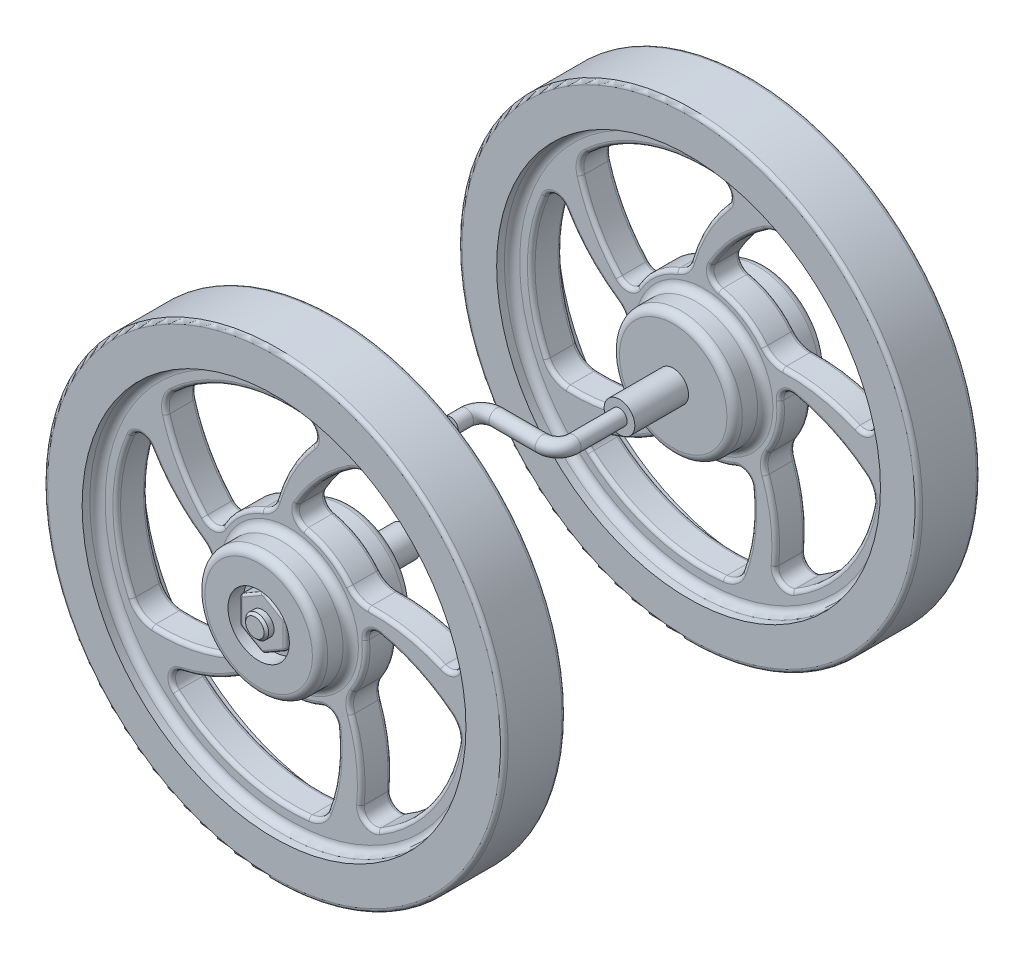
SolidWorks part; units mm, degrees
material "AISI 1020"
ref_plane "Спереди" through (0, 0, 0) normal (0, 0, 1) x (1, 0, 0)
ref_plane "Сверху" through (0, 0, 0) normal (0, 1, 0) x (1, 0, 0)
ref_plane "Справа" through (0, 0, 0) normal (1, 0, 0) x (0, 0, -1)
sketch "Эскиз1" plane through (0, 0, 0) normal (0, 1, 0) x (1, 0, 0)
  line L0 (-352.3825, 0) -> (377.342, 0) construction
  line L1 (0, 174.0357) -> (0, -175.3971) construction
  line L2 (0, -140) -> (0, -80)
  line L3 (-20, -60) -> (-80, -60)
  line L4 (-100, -40) -> (-100, 40)
  line L5 (0, 140) -> (0, 80)
  line L6 (-20, 60) -> (-80, 60)
  arc A0 (-100, -40) -> (-80, -60) centre (-80, -40) ccw
  arc A1 (-20, -60) -> (0, -80) centre (-20, -80) cw
  arc A2 (-20, 60) -> (0, 80) centre (-20, 80) ccw
  arc A3 (-100, 40) -> (-80, 60) centre (-80, 40) cw
  point P13 (0, -60)
  point P21 (-100, 0)
  dimension "D4" = 20
  dimension "D1" = 140
  dimension "D2" = 80
  dimension "D3" = 100
ref_plane "Плоскость1" through (0, 0, 140) normal (0, 0, -1) x (-1, 0, 0)
sketch "Эскиз2" plane through (0, 0, 140) normal (0, 0, -1) x (-1, 0, 0)
  circle A0 centre (0, 0) radius 10
  dimension "D1" = 20
sweep "По траектории1" add profiles "Эскиз2" path "Эскиз1"
sketch "Эскиз3" plane through (0, 0, 0) normal (0, 1, 0) x (1, 0, 0)
  line L0 (0, 150.9872) -> (0, -160.0129) construction
  line L1 (-100, 40) -> (-100, -40) construction
  line L2 (-110, 40) -> (-90, 40) construction
  line L3 (-110, -40) -> (-90, -40) construction
  line L4 (-166.6895, 0) -> (41.4175, 0) construction
  line L5 (-90, -40) -> (-90, 40) construction
  line L6 (-90, 20) -> (-95, 20)
  line L7 (-90, 20) -> (-90, -20)
  line L9 (-95, 20) -> (-95, -20)
  line L10 (-90, -20) -> (-95, -20)
  point P18 (-90, 0)
  point P19 (-95, 0)
  dimension "D1" = 20
  dimension "D2" = 5
revolve "Вырез-Повернуть1" cut sketch "Эскиз3" angle 360 about L1
sketch "Эскиз4" plane through (0, 0, 0) normal (1, 0, 0) x (0, 0, -1)
  line L0 (0, 86.383) -> (0, -119.6609) construction
  line L1 (-305.5987, 0) -> (289.4148, 0) construction
  line L2 (140, 0) -> (140, 20)
  line L3 (-140, 0) -> (-210, 0)
  line L4 (-140, 0) -> (-140, 20)
  line L5 (-140, 20) -> (-210, 20)
  line L6 (-210, 0) -> (-210, 20)
  line L7 (140, 0) -> (210, 0)
  line L8 (140, 20) -> (210, 20)
  line L9 (210, 0) -> (210, 20)
  dimension "D1" = 20
  dimension "D2" = 210
revolve "Повернуть1" add sketch "Эскиз4" angle 360 about L1
sketch "Эскиз5" plane through (0, 0, 0) normal (1, 0, 0) x (0, 0, -1)
  line L0 (-556.9383, 0) -> (336.2092, 0) construction
  line L1 (0, 98.9939) -> (0, -140.8119) construction
  line L2 (-270, 411.7302) -> (-270, -180.2981) construction
  line L3 (-210, 20) -> (-210, -20) construction
  line L4 (-210, 0) -> (-210, 70)
  line L5 (-220, 80) -> (-240, 80)
  line L6 (-250, 90) -> (-250, 240)
  line L7 (-240, 250) -> (-230, 250)
  line L8 (-230, 250) -> (-230, 300)
  line L9 (-230, 300) -> (-310, 300)
  line L10 (-320, 80) -> (-300, 80)
  line L11 (-290, 90) -> (-290, 240)
  line L12 (-300, 250) -> (-310, 250)
  line L13 (-310, 250) -> (-310, 300)
  line L14 (-330, 70) -> (-330, 40)
  line L15 (-330, 40) -> (-310, 40)
  line L16 (-310, 40) -> (-310, 0)
  line L17 (-310, 0) -> (-210, 0)
  line L18 (230, 250) -> (230, 300)
  line L19 (240, 250) -> (230, 250)
  line L20 (250, 90) -> (250, 240)
  line L21 (220, 80) -> (240, 80)
  line L22 (210, 0) -> (210, 70)
  line L23 (310, 0) -> (210, 0)
  line L24 (310, 40) -> (310, 0)
  line L25 (330, 40) -> (310, 40)
  line L26 (330, 70) -> (330, 40)
  line L27 (320, 80) -> (300, 80)
  line L28 (290, 90) -> (290, 240)
  line L29 (300, 250) -> (310, 250)
  line L30 (310, 250) -> (310, 300)
  line L31 (230, 300) -> (310, 300)
  arc A0 (-250, 240) -> (-240, 250) centre (-240, 240) cw
  arc A1 (-250, 90) -> (-240, 80) centre (-240, 90) ccw
  arc A2 (-210, 70) -> (-220, 80) centre (-220, 70) ccw
  arc A3 (-330, 70) -> (-320, 80) centre (-320, 70) cw
  arc A4 (-290, 90) -> (-300, 80) centre (-300, 90) cw
  arc A5 (-290, 240) -> (-300, 250) centre (-300, 240) ccw
  arc A6 (250, 240) -> (240, 250) centre (240, 240) ccw
  arc A7 (250, 90) -> (240, 80) centre (240, 90) cw
  arc A8 (210, 70) -> (220, 80) centre (220, 70) cw
  arc A9 (330, 70) -> (320, 80) centre (320, 70) ccw
  arc A10 (290, 90) -> (300, 80) centre (300, 90) ccw
  arc A11 (290, 240) -> (300, 250) centre (300, 240) cw
  point P35 (-270, 300)
  dimension "D7" = 10
  dimension "D1" = 60
  dimension "D2" = 300
  dimension "D3" = 80
  dimension "D4" = 20
  dimension "D5" = 40
  dimension "D6" = 50
  dimension "D8" = 40
  dimension "D9" = 20
revolve "Повернуть2" add sketch "Эскиз5" angle 360 about L0
fillet "Скругление1" radius 5 4 edges at (300, 0, -230) (300, 0, -310) (300, 0, 230) (300, 0, 310)
sketch "Эскиз6" plane through (0, 0, 310) normal (0, 0, 1) x (1, 0, 0)
  line L0 (0, 322.762) -> (0, -326.0866) construction
  line L2 (-2.5, 33.1976) -> (-27.5, 18.7639)
  line L3 (-30, 14.4338) -> (-30, -14.4338)
  line L4 (-27.5, -18.7639) -> (-2.5, -33.1976)
  line L5 (2.5, -33.1976) -> (27.5, -18.7639)
  line L6 (30, -14.4338) -> (30, 14.4338)
  line L7 (27.5, 18.7639) -> (2.5, 33.1976)
  circle A0 centre (0, 0) radius 30 construction
  arc A1 (27.5, 18.7639) -> (30, 14.4338) centre (25, 14.4338) cw
  arc A2 (30, -14.4338) -> (27.5, -18.7639) centre (25, -14.4338) cw
  arc A3 (2.5, -33.1976) -> (-2.5, -33.1976) centre (0, -28.8675) cw
  arc A4 (-27.5, -18.7639) -> (-30, -14.4338) centre (-25, -14.4338) cw
  arc A5 (-30, 14.4338) -> (-27.5, 18.7639) centre (-25, 14.4338) cw
  arc A6 (-2.5, 33.1976) -> (2.5, 33.1976) centre (0, 28.8675) cw
  point P25 (0, 34.641)
  dimension "D2" = 5
  dimension "D1" = 60
extrude "Бобышка-Вытянуть1" add sketch "Эскиз6" along normal blind 15
fillet "Скругление2" radius 3 12 edges at (29.3301, 16.9338, 325) (30, 0, 325) (29.3301, -16.9338, 325) (15, -25.9808, 325) (0, -33.8675, 325) (-15, -25.9808, 325) (-29.3301, -16.9338, 325) (-30, 0, 325) (-29.3301, 16.9338, 325) (-15, 25.9808, 325) (0, 33.8675, 325) (15, 25.9808, 325)
mirror "Зеркальное отражение1" about plane through (0, 0, 0) normal (0, 0, 1) of "Скругление2", "Бобышка-Вытянуть1"
sketch "Эскиз7" plane through (0, 0, 0) normal (1, 0, 0) x (0, 0, -1)
  line L0 (-417.5127, 0) -> (393.1324, 0) construction
  line L1 (-325, 14.4338) -> (-325, -14.4338) construction
  line L2 (-325, 15) -> (-332, 15)
  line L3 (-325, 15) -> (-325, 0)
  line L4 (-325, 0) -> (-335, 0)
  line L5 (-335, 12) -> (-335, 0)
  line L6 (-332, 15) -> (-335, 12)
  line L7 (0, 58.5666) -> (0, -39.0851) construction
  line L8 (325, 0) -> (335, 0)
  line L9 (325, 15) -> (325, 0)
  line L10 (325, 15) -> (332, 15)
  line L11 (332, 15) -> (335, 12)
  line L12 (335, 12) -> (335, 0)
  point P6 (-335, 15)
  dimension "D1" = 15
  dimension "D2" = 10
revolve "Повернуть3" add sketch "Эскиз7" angle 360 about L0
sketch "Эскиз8" plane through (0, 0, 290) normal (0, 0, 1) x (1, 0, 0)
  line L0 (0, 326.6407) -> (0, -339.3849) construction
  line L1 (0, 0) -> (297.8131, 171.9425) construction
  line L2 (0, 0) -> (142.8639, 306.3725) construction
  line L3 (0, 0) -> (325.2178, 28.4529) construction
  arc A0 (20.1186, 97.9553) -> (78.1329, 62.4119) centre (0, 0) cw
  arc A1 (111.0747, 195.6717) -> (219.4131, 49.8288) centre (0, 0) cw
  arc A2 (10.0994, 120.0672) -> (79.6788, 194.5803) centre (201.3091, 11.2607) cw
  arc A3 (102.6329, 51.1542) -> (198.7613, 32.7697) centre (110.4066, -168.7084) cw
  arc A4 (111.0747, 195.6717) -> (79.6788, 194.5803) centre (96.2647, 169.5821) ccw
  arc A5 (102.6329, 51.1542) -> (78.1329, 62.4119) centre (101.5728, 81.1355) cw
  arc A6 (219.4131, 49.8288) -> (198.7613, 32.7697) centre (204.7855, 46.5069) cw
  arc A7 (10.0994, 120.0672) -> (20.1186, 97.9553) centre (23.1364, 112.6486) ccw
  arc A8 (117.3116, 27.4977) -> (99.378, 11.1359) centre (114.2847, 12.8063) ccw
  arc A9 (117.3116, 27.4977) -> (209.6789, -15.6504) centre (72.9175, -187.9765) cw
  arc A10 (220.4188, -45.1724) -> (209.6789, -15.6504) centre (191.0296, -39.1494) ccw
  arc A11 (220.4188, -45.1724) -> (115.1923, -193.2763) centre (0, 0) cw
  arc A12 (115.1923, -193.2763) -> (92.5865, -178.9069) centre (107.5129, -180.3912) cw
  arc A13 (80.3658, -81.8021) -> (92.5865, -178.9069) centre (-126.3337, -157.1366) cw
  arc A14 (80.3658, -81.8021) -> (83.5016, -55.0225) centre (108.5521, -71.5292) cw
  arc A15 (99.378, 11.1359) -> (83.5016, -55.0225) centre (0, 0) cw
  arc A16 (62.4032, -103.0727) -> (41.3004, -91.0729) centre (47.4954, -104.7339) ccw
  arc A17 (62.4032, -103.0727) -> (49.9099, -204.2528) centre (-156.2436, -127.4366) cw
  arc A18 (25.1517, -223.5898) -> (49.9099, -204.2528) centre (21.7981, -193.7778) ccw
  arc A19 (25.1517, -223.5898) -> (-148.2203, -169.2801) centre (0, 0) cw
  arc A20 (-148.2203, -169.2801) -> (-141.5397, -143.3402) centre (-138.3389, -157.9948) cw
  arc A21 (-52.964, -101.7107) -> (-141.5397, -143.3402) centre (-188.4851, 71.5926) cw
  arc A22 (-52.964, -101.7107) -> (-26.5261, -96.4177) centre (-34.4839, -125.343) cw
  arc A23 (41.3004, -91.0729) -> (-26.5261, -96.4177) centre (0, 0) cw
  arc A24 (-78.7443, -91.2002) -> (-73.853, -67.4221) centre (-84.9309, -77.5354) ccw
  arc A25 (-78.7443, -91.2002) -> (-178.8329, -110.5847) centre (-169.4813, 109.2164) cw
  arc A26 (-204.8742, -93.0137) -> (-178.8329, -110.5847) centre (-177.5577, -80.6119) ccw
  arc A27 (-204.8742, -93.0137) -> (-206.7975, 88.6554) centre (0, 0) cw
  arc A28 (-206.7975, 88.6554) -> (-180.0629, 90.3177) centre (-193.011, 82.7451) cw
  arc A29 (-113.0994, 18.9415) -> (-180.0629, 90.3177) centre (9.8435, 201.3833) cw
  arc A30 (-113.0994, 18.9415) -> (-99.8957, -4.5669) centre (-129.8644, -5.937) cw
  arc A31 (-73.853, -67.4221) -> (-99.8957, -4.5669) centre (0, 0) cw
  arc A32 (-111.0698, 46.7079) -> (-86.944, 49.4038) centre (-99.9856, 56.8144) ccw
  arc A33 (-111.0698, 46.7079) -> (-160.4347, 135.9076) centre (51.4984, 194.936) cw
  arc A34 (-151.7709, 166.1042) -> (-160.4347, 135.9076) centre (-131.5348, 143.9569) ccw
  arc A35 (-151.7709, 166.1042) -> (20.4124, 224.0722) centre (0, 0) cw
  arc A36 (20.4124, 224.0722) -> (30.2548, 199.1597) centre (19.0516, 209.134) cw
  arc A37 (-16.9352, 113.4172) -> (30.2548, 199.1597) centre (194.5687, 52.8691) cw
  arc A38 (-16.9352, 113.4172) -> (-35.2128, 93.5952) centre (-45.7767, 121.6737) cw
  arc A39 (-86.944, 49.4038) -> (-35.2128, 93.5952) centre (0, 0) cw
  point P15 (95.0891, 203.9193)
  point P18 (86.6025, 50)
  point P21 (224.1438, 19.61)
  point P24 (0, 100)
  point P84 (0, 0)
  dimension "D2" = 100
  dimension "D5" = 125
  dimension "D6" = 220
  dimension "D7" = 220
  dimension "D8" = 30
  dimension "D9" = 15
  dimension "D1" = 60
  dimension "D3" = 25
  dimension "D4" = 60
  dimension "D10" = 5
extrude "Вырез-Вытянуть1" cut sketch "Эскиз8" against normal up to surface (40 mm away) up to face at (240, 0, 250)
fillet "Скругление3" radius 5 80 edges at (40.5133, 161.4097, 250) (95.2224, 199.564, 250) (180.6186, 134.1713, 250) (214.3384, 34.9421, 250) (151.7324, 47.3753, 250) (89.0469, 53.8756, 250) (52.2415, 85.2691, 250) (78.7557, -68.0402, 250) (97.2393, -23.335, 250) (104.1748, 23.8874, 250) (166.0291, 11.3479, 250) (219.222, -28.8932, 250) (183.4187, -130.3173, 250) (99.4662, -193.0502, 250) (-152.8649, -154.2537, 250) (-94.9076, -127.5135, 250) (-40.3732, -95.9267, 250) (7.8557, -99.691, 250) (54.91, -91.6946, 250) (62.0983, -154.3964, 250) (40.2642, -217.421, 250) (-160.3713, 152.2306, 250) (-71.7902, 213.2397, 250) (33.0023, 214.6456, 250) (1.8313, 158.9459, 250) (-23.7217, 101.3371, 250) (-64.9523, 76.0342, 250) (-98.3199, 41.9071, 250) (-193.9419, 97.7162, 250) (-150.6006, 50.8586, 250) (-103.7077, 8.7542, 250) (-92.3842, -38.2774, 250) (-70.2386, -80.5577, 250) (-127.6503, -106.7701, 250) (-194.3374, -105.4804, 250) (40.2642, -217.421, 290) (-67.2596, -214.7118, 290) (-152.8649, -154.2537, 290) (-94.9076, -127.5135, 290) (-40.3732, -95.9267, 290) (7.8557, -99.691, 290) (54.91, -91.6946, 290) (219.222, -28.8932, 290) (183.4187, -130.3173, 290) (99.4662, -193.0502, 290) (91.9445, -129.6663, 290) (78.7557, -68.0402, 290) (97.2393, -23.335, 290) (104.1748, 23.8874, 290) (95.2224, 199.564, 290) (180.6186, 134.1713, 290) (214.3384, 34.9421, 290) (151.7324, 47.3753, 290) (89.0469, 53.8756, 290) (52.2415, 85.2691, 290) (9.4736, 106.4578, 290) (-160.3713, 152.2306, 290) (-71.7902, 213.2397, 290) (33.0023, 214.6456, 290) (1.8313, 158.9459, 290) (-23.7217, 101.3371, 290) (-64.9523, 76.0342, 290) (-98.3199, 41.9071, 290) (-194.3374, -105.4804, 290) (-224.9874, -2.3819, 290) (-193.9419, 97.7162, 290) (-150.6006, 50.8586, 290) (-103.7077, 8.7542, 290) (-92.3842, -38.2774, 290) (-70.2386, -80.5577, 290) (9.4736, 106.4578, 250) (91.9445, -129.6663, 250) (-67.2596, -214.7118, 250) (-140.9905, 88.4088, 250) (-224.9874, -2.3819, 250) (62.0983, -154.3964, 290) (166.0291, 11.3479, 290) (40.5133, 161.4097, 290) (-140.9905, 88.4088, 290) (-127.6503, -106.7701, 290)
mirror "Зеркальное отражение3" about plane through (0, 0, 0) normal (0, 0, 1) of "Скругление3", "Вырез-Вытянуть1"
